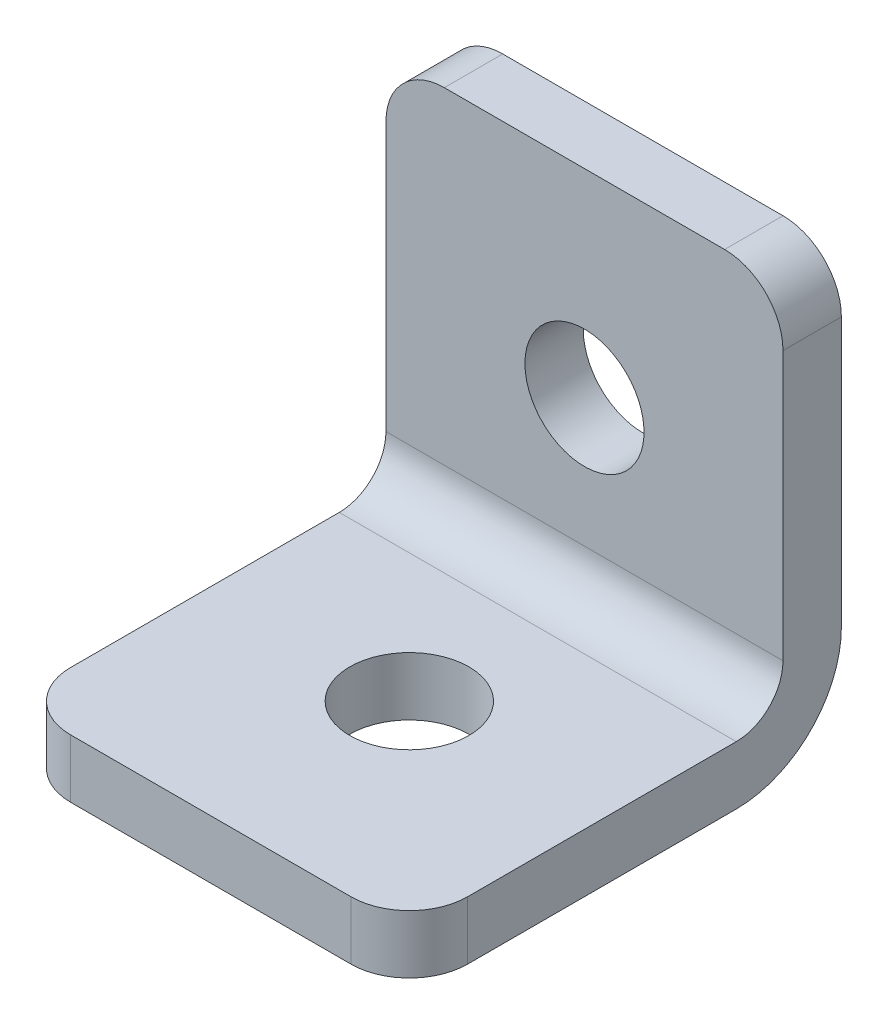
SolidWorks part; units mm, degrees
material "AISI 4340 Steel, normalized"
ref_plane "Спереди" through (0, 0, 0) normal (0, 0, 1) x (1, 0, 0)
ref_plane "Сверху" through (0, 0, 0) normal (0, 1, 0) x (1, 0, 0)
ref_plane "Справа" through (0, 0, 0) normal (1, 0, 0) x (0, 0, -1)
sketch "Эскиз1" plane through (0, 0, 0) normal (1, 0, 0) x (0, 0, -1)
  line L0 (14, 2.5) -> (0, 2.5)
  line L1 (0, 0) -> (0, 18.5) construction
  line L2 (18.5, 18.5) -> (18.5, 4.5)
  line L3 (14, 0) -> (0, 0)
  line L4 (18.5, 18.5) -> (0, 18.5) construction
  line L5 (0, 0) -> (0, 2.5)
  line L6 (16, 18.5) -> (18.5, 18.5)
  line L9 (16, 18.5) -> (16, 4.5)
  arc A0 (18.5, 4.5) -> (14, 0) centre (14, 4.5) cw
  arc A1 (16, 4.5) -> (14, 2.5) centre (14, 4.5) cw
  dimension "D3" = 4.5
  dimension "D5" = 2
  dimension "D1" = 18.5
  dimension "D2" = 18.5
  dimension "D4" = 2.5
  dimension "D6" = 2.5
extrude "Base" add sketch "Эскиз1" along normal blind 17
fillet "Fillet" radius 2.5 4 edges at (0, 18.5, -17.25) (17, 18.5, -17.25) (17, 1.25, 0) (0, 1.25, 0)
sketch "Эскиз2" plane through (0, 0, 0) normal (0, -1, 0) x (1, 0, 0)
  line L0 (8.5, 0) -> (8.5, -19.0977) construction
  line L1 (14.5, 0) -> (2.5, 0) construction
  line L2 (4.7982, -8.5) -> (12.8187, -8.5) construction
  line L3 (17, -18.5) -> (0, -18.5) construction
  circle A0 centre (8.5, -8.5) radius 2.55
  dimension "D2" = 5.1
  dimension "D1" = 10
extrude "Hole1" cut sketch "Эскиз2" against normal blind 17
sketch "Эскиз3" plane through (0, 0, -18.5) normal (0, 0, -1) x (-1, 0, 0)
  line L0 (-8.5, 19.3587) -> (-8.5, -0.7401) construction
  line L1 (-12.5814, 10) -> (-4.466, 10) construction
  line L2 (-17, 0) -> (0, 0) construction
  line L4 (-17, 4.5) -> (-17, 16) construction
  circle A0 centre (-8.5, 10) radius 2.55
  dimension "D3" = 5.1
  dimension "D1" = 10
  dimension "D2" = 8.5
extrude "Hole2" cut sketch "Эскиз3" against normal blind 17
